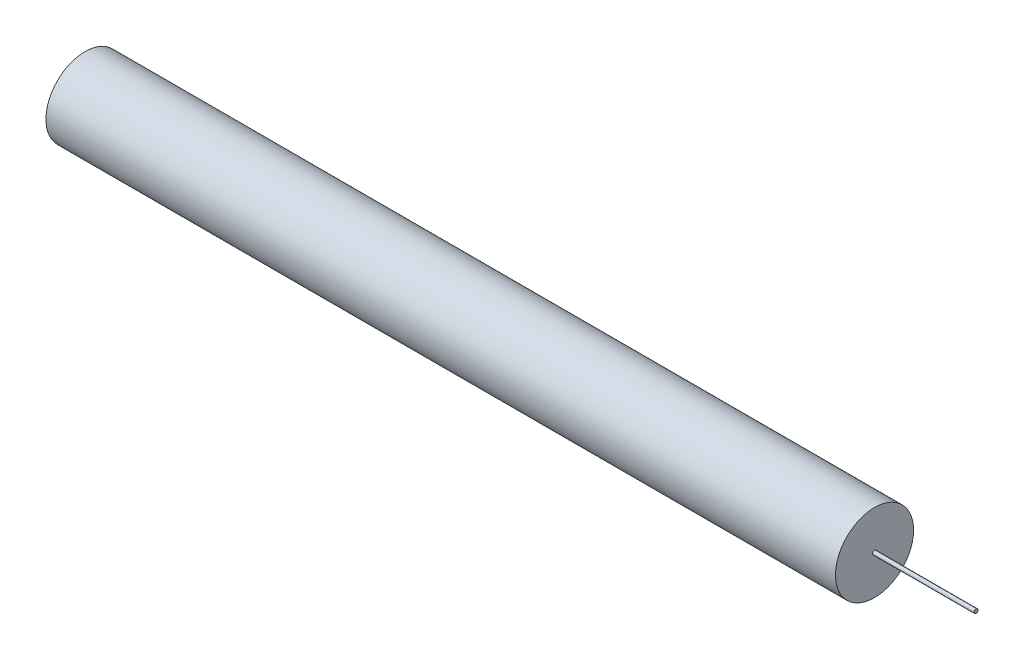
SolidWorks part; units mm, degrees
ref_plane "Front Plane" through (0, 0, 0) normal (0, 0, 1) x (1, 0, 0)
ref_plane "Top Plane" through (0, 0, 0) normal (0, 1, 0) x (1, 0, 0)
ref_plane "Right Plane" through (0, 0, 0) normal (1, 0, 0) x (0, 0, -1)
sketch "Sketch1" plane through (0, 0, 0) normal (0, 0, 1) x (1, 0, 0)
  line L0 (0, 0) -> (404.3572, 0)
  line L1 (0, 0) -> (456.3572, 0) construction
  point P4 (601.545, 0)
  point P5 (547.7215, 0)
  point P9 (456.3572, 0)
  dimension "D1" = 52
sketch "Sketch2" plane through (0, 0, 0) normal (1, 0, 0) x (0, 0, -1)
  circle A0 centre (0, 0) radius 20
  dimension "D1" = 40
sweep "Sweep1" add path "Sketch1" circular profile diameter 40 parameters "D3"=40
sketch "Sketch16" plane through (0, 0, 0) normal (0, 0, 1) x (1, 0, 0)
  line L0 (404.3572, -20) -> (404.3572, 20) construction
  line L1 (404.3572, -20) -> (404.3572, 20) construction
  line L2 (456.3572, 0) -> (404.3572, 0)
  point P2 (456.3572, 0)
sweep "Sweep2" add path "Sketch16" circular profile diameter 2 parameters "D3"=2
